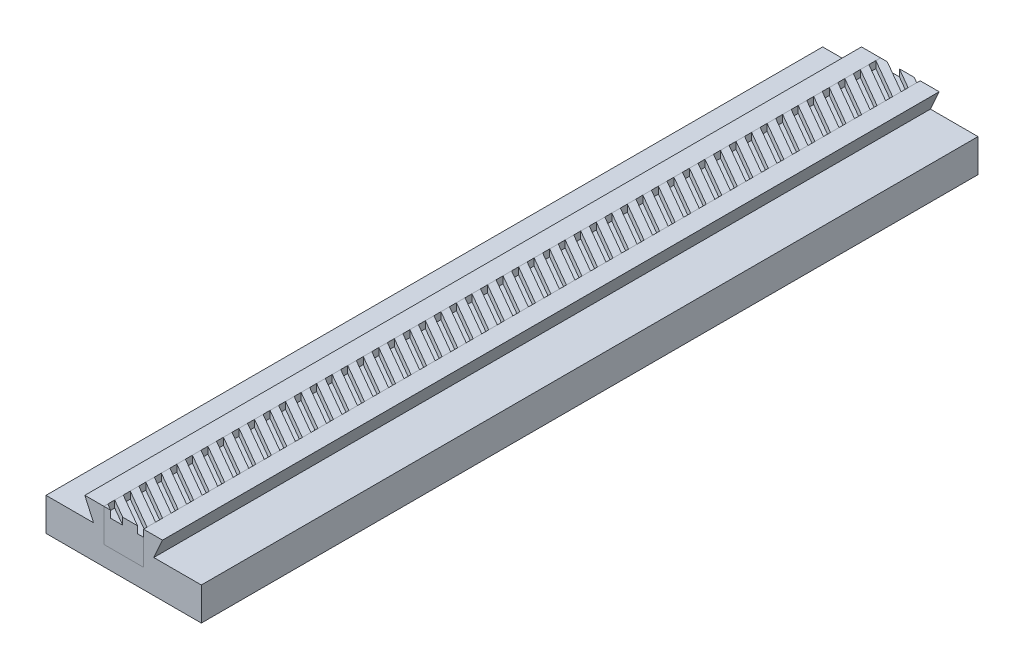
SolidWorks part; units mm, degrees
material "6061"
ref_plane "前视基准面" through (0, 0, 0) normal (0, 0, 1) x (1, 0, 0)
ref_plane "上视基准面" through (0, 0, 0) normal (0, 1, 0) x (1, 0, 0)
ref_plane "右视基准面" through (0, 0, 0) normal (1, 0, 0) x (0, 0, -1)
sketch "草图1" plane through (0, 0, 0) normal (0, 0, 1) x (1, 0, 0)
  line L0 (0, -419.1211) -> (0, 20536.9346) construction
  line L1 (20, 0) -> (-20, 0)
  line L2 (-20, 0) -> (-20, 8.5)
  line L3 (-20, 8.5) -> (-7.75, 8.5)
  line L4 (10, 13.5) -> (-10, 13.5)
  line L5 (-10, 13.5) -> (-7.75, 8.5)
  line L6 (10, 13.5) -> (7.75, 8.5)
  line L7 (20, 8.5) -> (7.75, 8.5)
  line L8 (20, 0) -> (20, 8.5)
  point P12 (0, 13.5)
  point P14 (0, 0)
  dimension "D1" = 40
  dimension "D2" = 8.5
  dimension "D3" = 13.5
  dimension "D4" = 20
  dimension "D5" = 15.5
extrude "凸台-拉伸1" add sketch "草图1" along normal blind 200
sketch "草图2" plane through (0, 0, 200) normal (0, 0, 1) x (1, 0, 0)
  line L0 (10, 13.5) -> (-10, 13.5) construction
  line L1 (-5.1, 5) -> (-5.1, 13.5)
  line L2 (5.1, 5) -> (5.1, 13.5)
  line L3 (5.1, 5) -> (-5.1, 5)
  line L5 (0, 13.5) -> (-5.1, 5) construction
  line L6 (5.1, 5) -> (0, 13.5) construction
  line L7 (0, 0) -> (0, 24.3041) construction
  point P0 (0, 13.5)
  dimension "D1" = 8.5
  dimension "D2" = 10.2
extrude "切除-拉伸1" cut sketch "草图2" against normal through all and the other way through all
sketch "草图3" plane through (0, 0, 0) normal (0, 0, -1) x (-1, 0, 0)
  line L1 (-5.1, 13.5) -> (5.1, 13.5)
  line L2 (-5.1, 13.5) -> (-5.1, 5)
  line L3 (-5.1, 5) -> (5.1, 5)
  line L4 (5.1, 13.5) -> (5.1, 5)
extrude "凸台-拉伸2" add sketch "草图3" against normal up to surface (200 mm away) separate body up to face at (0, 8.1667, 200)
sketch "草图4" plane through (0, 13.5, 0) normal (0, 1, 0) x (1, 0, 0)
  line L0 (0, 0) -> (0, -200) construction
  line L1 (5.1, -200) -> (-5.1, -200) construction
  line L2 (-5.1, 6.8) -> (5.1, 0.911)
  line L3 (-5.1, -200) -> (-5.1, 0) construction
  line L4 (5.1, -200) -> (5.1, 0) construction
  line L5 (5.1, 0.911) -> (5.1, -0.889)
  line L6 (5.1, -200) -> (5.1, 0) construction
  line L7 (5.1, -0.889) -> (-5.1, 5)
  line L8 (-5.1, 5) -> (-5.1, 6.8)
  dimension "D1" = 1.8
  dimension "D2" = 5
  dimension "D3" = 120
extrude "切除-拉伸2" cut sketch "草图4" against normal blind 1.8
pattern_linear "阵列(线性)1" count 128 spacing 4 along (0, 0, 1) of "切除-拉伸2"
sketch "草图5" plane through (0, 0, 0) normal (0, -1, 0) x (1, 0, 0)
  line L0 (20, 0) -> (-20, 200) construction
  line L1 (-20, 0) -> (20, 200) construction
  line L2 (20, 100) -> (-20, 100) construction
  line L3 (0, 100) -> (-16, 100) construction
  line L4 (-20, 0) -> (20, 0)
  line L5 (20, 0) -> (20, 200)
  line L6 (20, 200) -> (-20, 200)
  line L7 (-20, 200) -> (-20, 0)
  line L8 (-20, 0) -> (20, 0) construction
  line L9 (20, 0) -> (20, 200) construction
  line L10 (20, 200) -> (-20, 200) construction
  line L11 (-20, 200) -> (-20, 0) construction
  line L12 (0, 100) -> (0, 138.8796) construction
  circle A0 centre (-16, 100) radius 2
  circle A1 centre (16, 100) radius 2
  circle A2 centre (-16, 175) radius 2
  circle A3 centre (16, 175) radius 2
  circle A4 centre (16, 25) radius 2
  circle A5 centre (-16, 25) radius 2
  dimension "D3" = 4
  dimension "D2" = 16
  dimension "D1" = 0
  dimension "D4" = 2
  dimension "D5" = 2
extrude "切除-拉伸3" cut sketch "草图5" against normal blind 5
